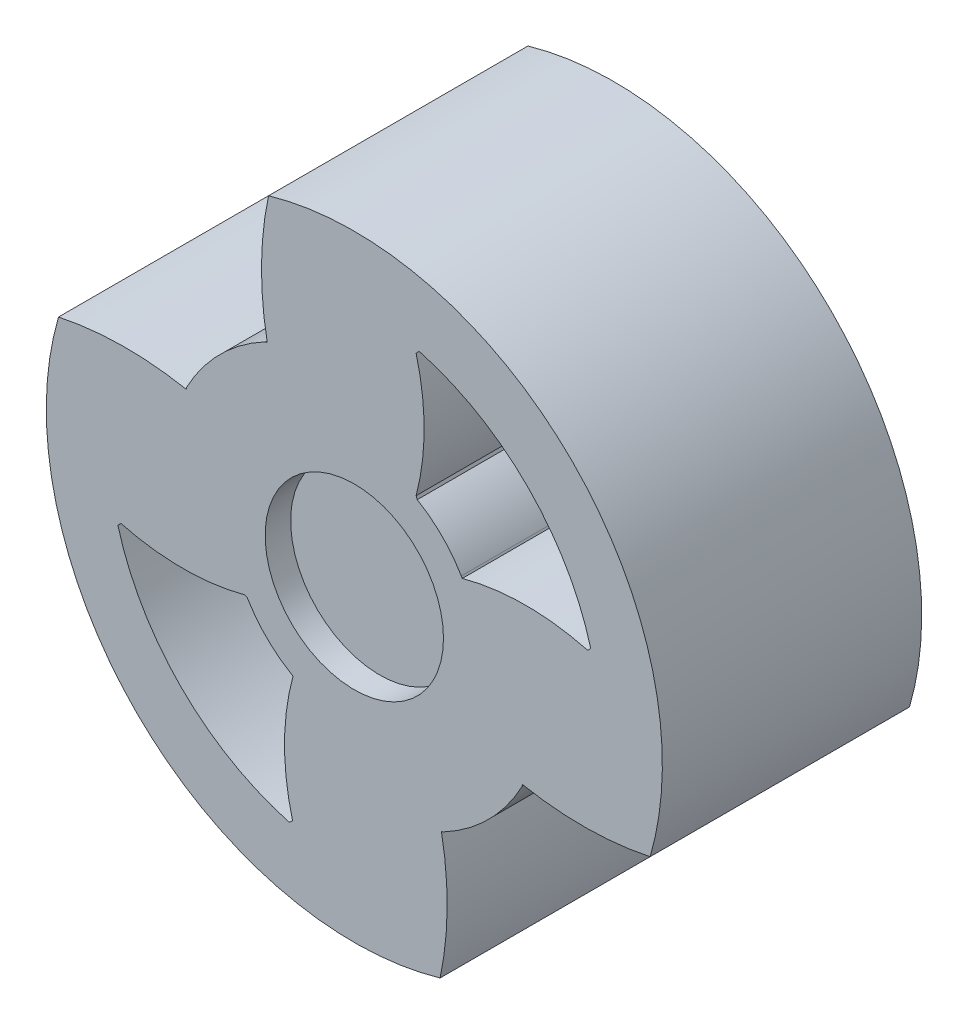
SolidWorks part; units mm, degrees
ref_plane "Front Plane" through (0, 0, 0) normal (0, 0, 1) x (1, 0, 0)
ref_plane "Top Plane" through (0, 0, 0) normal (0, 1, 0) x (1, 0, 0)
ref_plane "Right Plane" through (0, 0, 0) normal (1, 0, 0) x (0, 0, -1)
sketch "Sketch1" plane through (0, 0, 0) normal (0, 0, 1) x (1, 0, 0)
  line L0 (-6.5985, 3.4184) -> (-6.5875, 3.488)
  line L1 (-3.488, 6.5875) -> (-3.4184, 6.5985)
  line L2 (3.4184, -6.5985) -> (3.488, -6.5875)
  line L3 (6.5875, -3.488) -> (6.5985, -3.4184)
  arc A8 (3.3675, -11.6136) -> (3.4184, -6.5985) centre (-8.9803, -8.9803) ccw
  arc A9 (-6.5985, 3.4184) -> (3.4184, -6.5985) centre (0, 0) ccw
  arc A10 (-6.5985, 3.4184) -> (-11.6136, 3.3675) centre (-8.9803, -8.9803) ccw
  arc A11 (-11.6136, 3.3675) -> (3.3675, -11.6136) centre (0, 0) ccw
  arc A12 (3.3675, -11.6136) -> (3.4184, -6.5985) centre (-8.9803, -8.9803) ccw
  arc A14 (-6.5985, 3.4184) -> (-11.6136, 3.3675) centre (-8.9803, -8.9803) ccw
  arc A15 (-11.6136, 3.3675) -> (3.3675, -11.6136) centre (0, 0) ccw
  arc A18 (-3.488, 6.5875) -> (-6.5875, 3.488) centre (0, 0) ccw
  arc A19 (-3.488, 6.5875) -> (-6.5875, 3.488) centre (0, 0) ccw
  arc A20 (-3.3675, 11.6136) -> (-3.4184, 6.5985) centre (8.9803, 8.9803) ccw
  arc A21 (6.5985, -3.4184) -> (-3.4184, 6.5985) centre (0, 0) ccw
  arc A22 (6.5985, -3.4184) -> (11.6136, -3.3675) centre (8.9803, 8.9803) ccw
  arc A23 (11.6136, -3.3675) -> (-3.3675, 11.6136) centre (0, 0) ccw
  arc A24 (-3.3675, 11.6136) -> (-3.4184, 6.5985) centre (8.9803, 8.9803) ccw
  arc A26 (6.5985, -3.4184) -> (11.6136, -3.3675) centre (8.9803, 8.9803) ccw
  arc A27 (11.6136, -3.3675) -> (-3.3675, 11.6136) centre (0, 0) ccw
  arc A29 (3.488, -6.5875) -> (6.5875, -3.488) centre (0, 0) ccw
  arc A30 (3.488, -6.5875) -> (6.5875, -3.488) centre (0, 0) ccw
  dimension "D1" = 0.1
  dimension "D2" = 0.1
  dimension "D3" = 0.1
  dimension "D4" = 0.1
extrude "Boss-Extrude1" add sketch "Sketch1" along normal up to surface (10.1812 mm away)
sketch "Sketch2" plane through (0, 0, 0) normal (0, 0, -1) x (-1, 0, 0)
  circle A0 centre (0, 0) radius 5
  dimension "D1" = 10
extrude "Cut-Extrude1" cut sketch "Sketch2" against normal blind 1
sketch "Sketch3" plane through (0, 0, 10.1812) normal (0, 0, 1) x (1, 0, 0)
  line L0 (9.1595, 2.4252) -> (9.2815, 2.5484)
  line L1 (2.4252, 9.1595) -> (2.5484, 9.2815)
  line L2 (4.2001, 2.4715) -> (4.2387, 2.4058)
  line L3 (2.4715, 4.2001) -> (2.4255, 4.3119)
  arc A5 (2.4255, 4.3119) -> (2.4252, 9.1595) centre (-6.7352, 6.7352) ccw
  arc A6 (2.4255, 4.3119) -> (2.4252, 9.1595) centre (-6.7352, 6.7352) ccw
  arc A11 (9.2815, 2.5484) -> (2.5484, 9.2815) centre (0, 0) ccw
  arc A12 (9.2815, 2.5484) -> (2.5484, 9.2815) centre (0, 0) ccw
  arc A14 (9.1595, 2.4252) -> (8.7382, 2.5265) centre (6.7352, -6.7352) ccw
  arc A15 (9.1595, 2.4252) -> (8.7382, 2.5265) centre (6.7352, -6.7352) ccw
  arc A16 (8.7382, 2.5265) -> (4.0919, 2.3645) centre (6.7352, -6.7352) ccw
  arc A17 (4.2001, 2.4715) -> (2.4715, 4.2001) centre (0, 0) ccw
  arc A18 (4.2001, 2.4715) -> (2.4715, 4.2001) centre (0, 0) ccw
  arc A19 (8.7382, 2.5265) -> (4.2387, 2.4058) centre (6.7352, -6.7352) ccw
  dimension "D1" = 0.1
  dimension "D2" = 0.1
  dimension "D3" = 0.1
  dimension "D4" = 0.1
  dimension "D5" = 0.1
extrude "Cut-Extrude2" cut sketch "Sketch3" against normal blind 7.5
ref_plane "Plane1" through (0, 0, 0) normal (0.7071, 0.7071, 0) x (0.7071, -0.7071, 0)
mirror "Mirror1" about plane through (0, 0, 0) normal (0.7071, 0.7071, 0) of "Cut-Extrude2"
sketch "Sketch4" plane through (0, 0, 10.1812) normal (0, 0, 1) x (1, 0, 0)
  circle A0 centre (0, 0) radius 3.5
  dimension "D1" = 7
extrude "Cut-Extrude3" cut sketch "Sketch4" against normal blind 1
